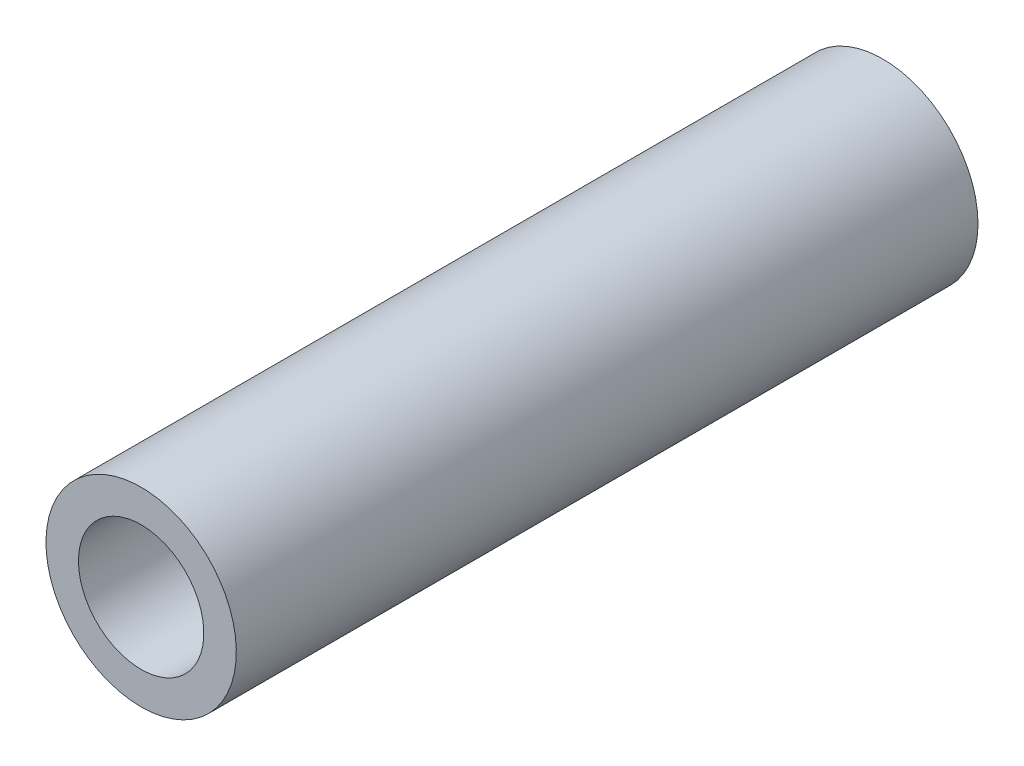
SolidWorks part; units mm, degrees
ref_plane "Front Plane" through (0, 0, 0) normal (0, 0, 1) x (1, 0, 0)
ref_plane "Top Plane" through (0, 0, 0) normal (0, 1, 0) x (1, 0, 0)
ref_plane "Right Plane" through (0, 0, 0) normal (1, 0, 0) x (0, 0, -1)
sketch "Sketch1" plane through (0, 0, 0) normal (0, 0, 1) x (1, 0, 0)
  circle A3 centre (59.4755, 35.57) radius 4.1
extrude "Boss-Extrude2" add sketch "Sketch1" along normal up to surface (31.95 mm away)
hole_wizard "M5 Clearance Hole1" positions "Sketch2" profile "Sketch3" hole size "M5" standard "ISO" end condition through all
sketch "Sketch2" plane through (0, 0, 0) normal (0, 0, -1) x (-1, 0, 0)
  point P0 (-59.4755, 35.57)
sketch "Sketch3" plane through (59.4755, 35.57, 0) normal (1, 0, 0) x (0, 1, 0)
  line L0 (0, 0) -> (0, 31.95)
  line L1 (0, 31.95) -> (2.7, 31.95)
  line L2 (2.7, 31.95) -> (2.7, 0)
  line L5 (2.7, 0) -> (0, 0)
  line L11 (0, -6.35) -> (0, 107.95) construction
  dimension "Thru Hole Dia." = 5.4
  dimension "Thru Hole Depth" = 31.95
